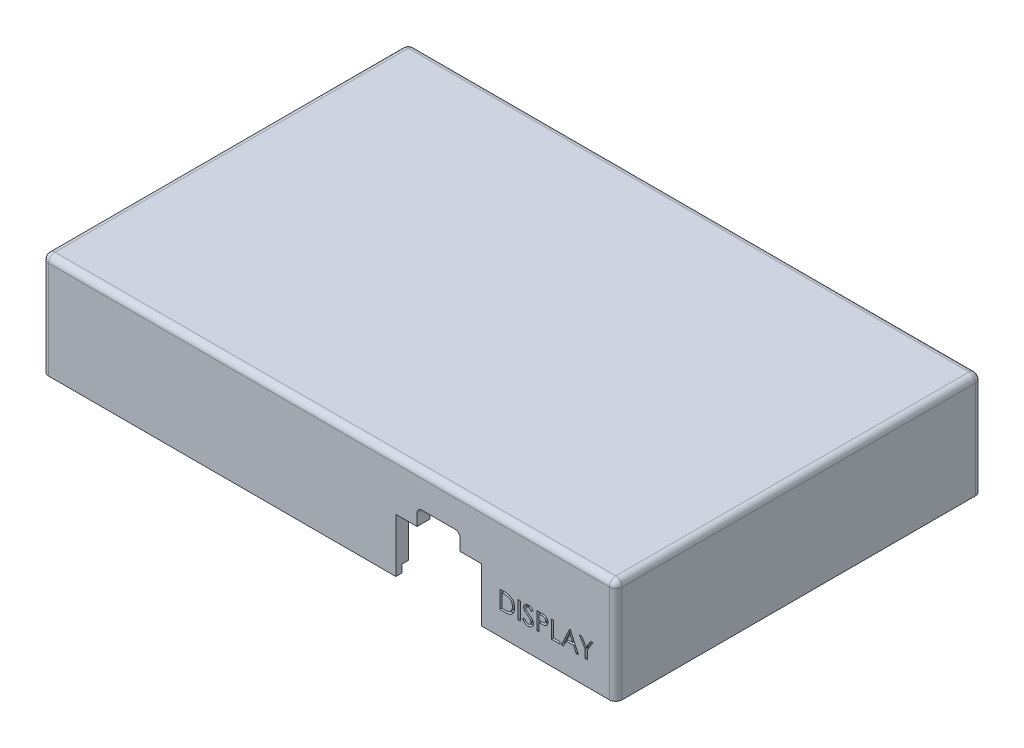
SolidWorks part; units mm, degrees
ref_plane "Front Plane" through (0, 0, 0) normal (0, 0, 1) x (1, 0, 0)
ref_plane "Top Plane" through (0, 0, 0) normal (0, 1, 0) x (1, 0, 0)
ref_plane "Right Plane" through (0, 0, 0) normal (1, 0, 0) x (0, 0, -1)
sketch "Sketch1" plane through (0, 0, 0) normal (0, 1, 0) x (1, 0, 0)
  line L7 (87.3207, 2.54) -> (87.3207, 0) construction
  line L8 (70.3047, 2.54) -> (70.3047, 0) construction
  line L9 (87.3207, 0) -> (112.776, 0) construction
  line L10 (2.54, 60.5853) -> (2.54, 44.8735) construction
  line L11 (2.54, 44.8735) -> (0, 44.8735) construction
  line L12 (2.54, 12.1857) -> (12.1856, 12.1857) construction
  line L22 (12.1856, 12.1857) -> (12.1856, 2.54) construction
  line L23 (12.1856, 2.54) -> (70.3047, 2.54) construction
  line L24 (101.8603, 12.1857) -> (101.8603, 2.54) construction
  line L25 (111.506, 12.1857) -> (101.8603, 12.1857) construction
  line L28 (111.506, 12.1857) -> (111.506, 60.5853) construction
  line L29 (1.27, 0) -> (70.3047, 0) construction
  line L30 (114.046, 1.27) -> (114.046, 71.501) construction
  line L31 (111.506, 60.5853) -> (101.8603, 60.5853) construction
  line L32 (101.8603, 60.5853) -> (101.8603, 70.231) construction
  line L33 (12.1856, 60.5853) -> (2.54, 60.5853) construction
  line L34 (12.1856, 60.5853) -> (12.1856, 70.231) construction
  line L35 (0, 71.501) -> (0, 44.8735) construction
  line L36 (112.776, 72.771) -> (1.27, 72.771) construction
  line L37 (2.54, 12.1857) -> (2.54, 27.8575) construction
  line L38 (2.54, 27.8575) -> (0, 27.8575) construction
  line L39 (0, 27.8575) -> (0, 1.27) construction
  line L40 (87.3207, 2.54) -> (101.8603, 2.54) construction
  line L41 (12.1856, 70.231) -> (101.8603, 70.231) construction
  circle A4 centre (105.283, 64.008) radius 2.15 construction
  arc A5 (112.776, 0) -> (114.046, 1.27) centre (112.776, 1.27) ccw construction
  arc A6 (114.046, 71.501) -> (112.776, 72.771) centre (112.776, 71.501) ccw construction
  arc A7 (1.27, 72.771) -> (0, 71.501) centre (1.27, 71.501) ccw construction
  circle A8 centre (8.763, 64.008) radius 2.15 construction
  circle A9 centre (105.283, 8.763) radius 2.15 construction
  circle A10 centre (8.763, 8.763) radius 2.15 construction
  arc A11 (0, 1.27) -> (1.27, 0) centre (1.27, 1.27) ccw construction
sketch "Sketch5" plane through (0, 0, 0) normal (0, 1, 0) x (1, 0, 0)
  line L0 (2.54, 27.8575) -> (0, 27.8575) construction
  line L1 (0, 27.8575) -> (0, 1.27) construction
  line L2 (2.54, 12.1857) -> (2.54, 27.8575) construction
  line L3 (2.54, 12.1857) -> (12.1856, 12.1857) construction
  line L4 (12.1856, 12.1857) -> (12.1856, 2.54) construction
  line L5 (1.27, 0) -> (70.3047, 0) construction
  line L6 (70.3047, 2.54) -> (70.3047, 0) construction
  line L7 (12.1856, 2.54) -> (70.3047, 2.54) construction
  line L8 (87.3207, 0) -> (112.776, 0) construction
  line L9 (87.3207, 2.54) -> (87.3207, 0) construction
  line L10 (87.3207, 2.54) -> (101.8603, 2.54) construction
  line L11 (101.8603, 12.1857) -> (101.8603, 2.54) construction
  line L12 (111.506, 12.1857) -> (101.8603, 12.1857) construction
  line L13 (111.506, 12.1857) -> (111.506, 60.5853) construction
  line L14 (0, 71.501) -> (0, 44.8735) construction
  line L15 (2.54, 44.8735) -> (0, 44.8735) construction
  line L16 (2.54, 60.5853) -> (2.54, 44.8735) construction
  line L17 (12.1856, 60.5853) -> (2.54, 60.5853) construction
  line L18 (12.1856, 60.5853) -> (12.1856, 70.231) construction
  line L19 (12.1856, 70.231) -> (101.8603, 70.231) construction
  line L20 (101.8603, 60.5853) -> (101.8603, 70.231) construction
  line L21 (111.506, 60.5853) -> (101.8603, 60.5853) construction
  line L22 (114.046, 1.27) -> (114.046, 71.501) construction
  line L23 (112.776, 72.771) -> (1.27, 72.771) construction
  line L24 (2.54, 27.8575) -> (0, 27.8575)
  line L25 (0, 27.8575) -> (0, 1.27)
  line L26 (2.54, 12.1857) -> (2.54, 27.8575)
  line L27 (2.54, 12.1857) -> (12.1856, 12.1857)
  line L28 (12.1856, 12.1857) -> (12.1856, 2.54)
  line L29 (1.27, 0) -> (70.3047, 0)
  line L30 (70.3047, 2.54) -> (70.3047, 0)
  line L31 (12.1856, 2.54) -> (70.3047, 2.54)
  line L32 (87.3207, 0) -> (112.776, 0)
  line L33 (87.3207, 2.54) -> (87.3207, 0)
  line L34 (87.3207, 2.54) -> (101.8603, 2.54)
  line L35 (101.8603, 12.1857) -> (101.8603, 2.54)
  line L36 (111.506, 12.1857) -> (101.8603, 12.1857)
  line L37 (111.506, 12.1857) -> (111.506, 60.5853)
  line L38 (0, 71.501) -> (0, 44.8735)
  line L39 (2.54, 44.8735) -> (0, 44.8735)
  line L40 (2.54, 60.5853) -> (2.54, 44.8735)
  line L41 (12.1856, 60.5853) -> (2.54, 60.5853)
  line L42 (12.1856, 60.5853) -> (12.1856, 70.231)
  line L43 (12.1856, 70.231) -> (101.8603, 70.231)
  line L44 (101.8603, 60.5853) -> (101.8603, 70.231)
  line L45 (111.506, 60.5853) -> (101.8603, 60.5853)
  line L46 (114.046, 1.27) -> (114.046, 71.501)
  line L47 (112.776, 72.771) -> (1.27, 72.771)
  arc A0 (112.776, 0) -> (114.046, 1.27) centre (112.776, 1.27) ccw construction
  arc A1 (0, 1.27) -> (1.27, 0) centre (1.27, 1.27) ccw construction
  arc A2 (1.27, 72.771) -> (0, 71.501) centre (1.27, 71.501) ccw construction
  arc A3 (114.046, 71.501) -> (112.776, 72.771) centre (112.776, 71.501) ccw construction
  arc A4 (112.776, 0) -> (114.046, 1.27) centre (112.776, 1.27) ccw
  arc A5 (0, 1.27) -> (1.27, 0) centre (1.27, 1.27) ccw
  arc A6 (1.27, 72.771) -> (0, 71.501) centre (1.27, 71.501) ccw
  arc A7 (114.046, 71.501) -> (112.776, 72.771) centre (112.776, 71.501) ccw
extrude "Boss-Extrude3" add sketch "Sketch5" along normal blind 18.161
sketch "Sketch6" plane through (0, 18.161, 0) normal (0, 1, 0) x (1, 0, 0)
  line L0 (114.046, 1.27) -> (114.046, 71.501) construction
  line L1 (112.776, 72.771) -> (1.27, 72.771) construction
  line L2 (114.046, 1.27) -> (114.046, 71.501)
  line L3 (112.776, 72.771) -> (1.27, 72.771)
  line L4 (0, 1.27) -> (0, 71.501)
  line L5 (112.776, 0) -> (1.27, 0)
  arc A0 (0, 1.27) -> (1.27, 0) centre (1.27, 1.27) ccw construction
  arc A1 (112.776, 0) -> (114.046, 1.27) centre (112.776, 1.27) ccw construction
  arc A2 (114.046, 71.501) -> (112.776, 72.771) centre (112.776, 71.501) ccw construction
  arc A3 (1.27, 72.771) -> (0, 71.501) centre (1.27, 71.501) ccw construction
  arc A4 (0, 1.27) -> (1.27, 0) centre (1.27, 1.27) ccw
  arc A5 (112.776, 0) -> (114.046, 1.27) centre (112.776, 1.27) ccw
  arc A6 (114.046, 71.501) -> (112.776, 72.771) centre (112.776, 71.501) ccw
  arc A7 (1.27, 72.771) -> (0, 71.501) centre (1.27, 71.501) ccw
extrude "Boss-Extrude4" add sketch "Sketch6" along normal blind 2.54
hole_wizard "Tap Drill for M4x0.7 Tap1" positions "Sketch9" profile "Sketch8" hole size "M4x0.7" standard "ANSI Metric"
sketch "Sketch9" plane through (0, 0, 0) normal (0, -1, 0) x (-1, 0, 0)
  point P0 (-8.763, 8.763)
  point P2 (-8.763, 64.008)
  point P5 (-105.283, 64.008)
  point P8 (-105.283, 8.763)
sketch "Sketch8" plane through (8.763, 0, -8.763) normal (1, 0, 0) x (0, 0, -1)
  line L0 (0, 0) -> (0, 12.7)
  line L1 (0, 12.7) -> (1.65, 11.7086)
  line L2 (1.65, 11.7086) -> (1.65, 0)
  line L5 (1.65, 0) -> (0, 0)
  line L10 (0, 12.7) -> (-1.65, 11.7086) construction
  line L11 (0, -6.35) -> (0, 107.95) construction
  dimension "Hole Dia." = 3.3
  dimension "Hole Depth" = 12.7
  dimension "Drill Angle" = 118
sketch "Sketch10" plane through (0, 0, 0) normal (0, -1, 0) x (1, 0, 0)
  line L2 (2.54, -2.54) -> (70.3047, -2.54)
  line L3 (111.506, -12.1857) -> (111.506, -60.5853) construction
  line L7 (2.54, -60.5853) -> (2.54, -44.8735) construction
  line L8 (2.54, -70.231) -> (2.54, -44.8735)
  line L9 (12.1856, -2.54) -> (70.3047, -2.54) construction
  line L11 (2.54, -27.8575) -> (1.27, -27.8575)
  line L14 (1.27, -71.501) -> (1.27, -44.8735)
  line L15 (1.27, -1.27) -> (70.3047, -1.27)
  line L16 (2.54, -27.8575) -> (0, -27.8575) construction
  line L17 (2.54, -2.54) -> (111.506, -2.54) construction
  line L18 (1.27, -44.8735) -> (2.54, -44.8735)
  line L19 (2.54, -44.8735) -> (0, -44.8735) construction
  line L20 (70.3047, -1.27) -> (70.3047, -2.54)
  line L21 (70.3047, -2.54) -> (70.3047, 0) construction
  line L22 (87.3207, -1.27) -> (87.3207, -2.54)
  line L23 (87.3207, -2.54) -> (87.3207, 0) construction
  line L24 (87.3207, -1.27) -> (112.776, -1.27)
  line L25 (87.3207, -2.54) -> (111.506, -2.54)
  line L26 (1.27, -1.27) -> (112.776, -1.27) construction
  line L27 (1.27, -27.8575) -> (1.27, -1.27)
  line L28 (2.54, -27.8575) -> (2.54, -2.54)
  line L29 (1.27, -71.501) -> (1.27, -1.27) construction
  line L30 (2.54, -70.231) -> (111.506, -70.231)
  line L31 (2.54, -70.231) -> (2.54, -2.54) construction
  line L32 (112.776, -1.27) -> (112.776, -71.501) construction
  line L33 (111.506, -2.54) -> (111.506, -70.231) construction
  line L34 (111.506, -70.231) -> (2.54, -70.231) construction
  line L35 (112.776, -71.501) -> (1.27, -71.501) construction
  line L36 (111.506, -70.231) -> (111.506, -2.54)
  line L37 (1.27, -71.501) -> (112.776, -71.501)
  line L38 (112.776, -1.27) -> (112.776, -71.501)
  dimension "D1" = 1.27
extrude "Cut-Extrude5" cut sketch "Sketch10" against normal blind 1.524
sketch "Sketch11" plane through (0, 0, 0) normal (0, -1, 0) x (1, 0, 0)
  line L1 (2.54, -2.54) -> (12.1857, -2.54)
  line L2 (2.54, -2.54) -> (2.54, -12.1857)
  line L3 (2.54, -12.1857) -> (12.1856, -12.1857)
  line L4 (12.1857, -2.54) -> (12.1856, -12.1857)
  line L5 (101.8603, -12.1857) -> (111.506, -12.1857)
  line L6 (101.8603, -12.1857) -> (101.8603, -2.54)
  line L7 (101.8603, -2.54) -> (111.506, -2.54)
  line L8 (111.506, -12.1857) -> (111.506, -2.54)
  line L9 (101.8603, -60.5853) -> (111.506, -60.5853)
  line L10 (101.8603, -60.5853) -> (101.8603, -70.231)
  line L11 (101.8603, -70.231) -> (111.506, -70.231)
  line L12 (111.506, -60.5853) -> (111.506, -70.231)
  line L13 (12.1856, -60.5853) -> (2.54, -60.5853)
  line L14 (12.1856, -60.5853) -> (12.1856, -70.231)
  line L15 (12.1856, -70.231) -> (2.54, -70.231)
  line L16 (2.54, -60.5853) -> (2.54, -70.231)
extrude "Cut-Extrude6" cut sketch "Sketch11" against normal blind 0.254
sketch "Sketch12" plane through (0, 0, 0) normal (0, 0, 1) x (1, 0, 0)
  line L0 (70.3047, 18.161) -> (87.3207, 18.161)
  line L1 (87.3207, 18.161) -> (87.3207, 10.7214)
  line L2 (87.3207, 18.161) -> (87.3207, 0) construction
  line L3 (87.3207, 10.7214) -> (83.0909, 10.7214)
  line L4 (83.0909, 10.7214) -> (83.0909, 13.0154)
  line L5 (82.0749, 14.0314) -> (75.5449, 14.0314)
  line L6 (74.5289, 13.0154) -> (74.5289, 10.7214)
  line L7 (74.5289, 10.7214) -> (70.3047, 10.7214)
  line L8 (70.3047, 18.161) -> (70.3047, 0) construction
  line L9 (70.3047, 10.7214) -> (70.3047, 18.161)
  line L10 (75.6599, 13.6504) -> (81.9599, 13.6504) construction
  line L11 (82.7099, 12.5404) -> (82.7099, 10.8791) construction
  line L12 (74.9099, 12.5404) -> (74.9099, 10.8791) construction
  line L13 (71.5099, 10.3404) -> (73.0599, 10.3404) construction
  line L14 (82.7099, 10.3404) -> (86.1099, 10.3404) construction
  arc A0 (83.0909, 13.0154) -> (82.0749, 14.0314) centre (82.0749, 13.0154) ccw
  arc A1 (75.5449, 14.0314) -> (74.5289, 13.0154) centre (75.5449, 13.0154) ccw
  dimension "D4" = 1.016
  dimension "D1" = 0.381
  dimension "D2" = 0.381
  dimension "D3" = 0.381
  dimension "D5" = 0.381
  dimension "D6" = 0.381
extrude "Boss-Extrude5" add sketch "Sketch12" against normal up to surface (2.54 mm away) up to face at (41.2452, 9.8425, -2.54)
sketch "Sketch16" plane through (0, 0, 0) normal (-1, 0, 0) x (0, 0, 1)
  line L0 (-44.8735, 18.161) -> (-27.8575, 18.161)
  line L1 (-27.8575, 18.161) -> (-27.8575, 10.7214)
  line L2 (-27.8575, 18.161) -> (-27.8575, 0) construction
  line L3 (-27.8575, 10.7214) -> (-32.0848, 10.7214)
  line L4 (-32.0848, 10.7214) -> (-32.0848, 13.0154)
  line L5 (-33.1008, 14.0314) -> (-39.6308, 14.0314)
  line L6 (-40.6468, 13.0154) -> (-40.6468, 10.7214)
  line L7 (-40.6468, 10.7214) -> (-44.8735, 10.7214)
  line L8 (-44.8735, 18.161) -> (-44.8735, 0) construction
  line L9 (-44.8735, 10.7214) -> (-44.8735, 18.161)
  line L10 (-39.5158, 13.6504) -> (-33.2158, 13.6504) construction
  line L11 (-32.4658, 12.5404) -> (-32.4658, 10.8791) construction
  line L12 (-40.2658, 12.5404) -> (-40.2658, 10.8791) construction
  line L13 (-43.6658, 10.3404) -> (-42.1158, 10.3404) construction
  line L14 (-32.4658, 10.3404) -> (-29.0658, 10.3404) construction
  arc A0 (-32.0848, 13.0154) -> (-33.1008, 14.0314) centre (-33.1008, 13.0154) ccw
  arc A1 (-39.6308, 14.0314) -> (-40.6468, 13.0154) centre (-39.6308, 13.0154) ccw
  dimension "D6" = 1.016
  dimension "D1" = 0.381
  dimension "D2" = 0.381
  dimension "D3" = 0.381
  dimension "D4" = 0.381
  dimension "D5" = 0.381
extrude "Boss-Extrude6" add sketch "Sketch16" against normal up to surface (2.54 mm away) up to face at (2.54, 9.8425, -52.7294)
fillet "Fillet1" radius 1.27 8 edges at (0.372, 20.701, -0.372) (0, 20.701, -36.3855) (0.372, 20.701, -72.399) (57.023, 20.701, -72.771) (113.674, 20.701, -72.399) (114.046, 20.701, -36.3855) (113.674, 20.701, -0.372) (57.023, 20.701, 0)
fillet "Fillet2" radius 0.508 8 edges at (111.506, 0.254, -65.4082) (106.6832, 0.254, -70.231) (7.3628, 0.254, -70.231) (2.54, 0.254, -65.4082) (2.54, 1.524, -7.3628) (7.3628, 0.254, -2.54) (106.6832, 0.254, -2.54) (111.506, 0.254, -7.3628)
sketch "Sketch17" plane through (0, 0, 0) normal (0, 0, 1) x (1, 0, 0)
  text T0 "<b>DISPLAY</b>" font "Century Gothic" height 3.5
extrude "Cut-Extrude7" cut sketch "Sketch17" against normal blind 0.635
sketch "Sketch18" plane through (0, 0, 0) normal (-1, 0, 0) x (0, 0, 1)
  text T0 "<b>SENSORS</b>"
  text T1 "+POWER"
extrude "Cut-Extrude8" cut sketch "Sketch18" against normal blind 0.635
sketch "Sketch19" plane through (0, 0, -70.231) normal (0, 0, 1) x (1, 0, 0)
  line L1 (91.9672, 11.176) -> (18.933, 11.176) construction
  line L6 (1.27, 1.524) -> (112.776, 1.524) construction
  text T0 "<b>https://github.com/topolittle</b>"
  dimension "D1" = 9.652
extrude "Cut-Extrude9" cut sketch "Sketch19" against normal blind 0.635
